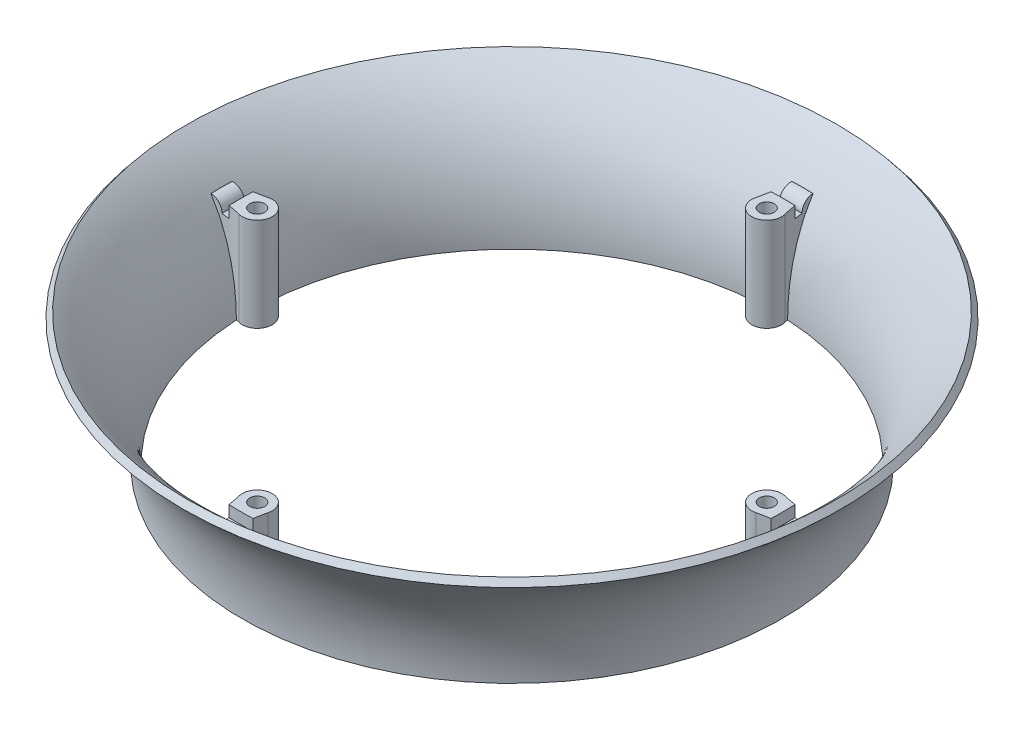
SolidWorks part; units mm, degrees
ref_plane "Front Plane" through (0, 0, 0) normal (0, 0, 1) x (1, 0, 0)
ref_plane "Top Plane" through (0, 0, 0) normal (0, 1, 0) x (1, 0, 0)
ref_plane "Right Plane" through (0, 0, 0) normal (1, 0, 0) x (0, 0, -1)
sketch "Sketch1" plane through (0, 0, 0) normal (0, 0, 1) x (1, 0, 0)
  line L0 (-25.5, 30) -> (-25.5, 0) construction
  line L1 (-25.5, 0) -> (-70, 0) construction
  line L2 (0, 0) -> (0, 35) construction
  line L3 (-70, 0) -> (-86.7157, 35) construction
  arc A0 (-70, 0) -> (-86.7157, 35) centre (-115, 0) ccw
  dimension "D1" = 35
  dimension "D5" = 45
  dimension "D2" = 30
  dimension "D3" = 70
  dimension "D4" = 25.5
  dimension "D7" = 35
revolve "Revolve-Thin1" add sketch "Sketch1" angle 360 about L2 wall 2
ref_plane "Plane1" through (0, 25, 0) normal (0, -1, 0) x (-1, 0, 0)
sketch "Sketch2" plane through (0, 25, 0) normal (0, -1, 0) x (-1, 0, 0)
  line L0 (-68, 0) -> (-86.7157, 0) construction
  line L1 (-86.7157, -4) -> (-86.7157, 4)
  line L2 (-4, 86.7157) -> (4, 86.7157)
  line L3 (0, 68) -> (0, 86.7157) construction
  line L4 (86.7157, 4) -> (86.7157, -4)
  line L5 (68, 0) -> (86.7157, 0) construction
  line L6 (4, -86.7157) -> (-4, -86.7157)
  line L7 (0, -68) -> (0, -86.7157) construction
  circle A0 centre (-68, 0) radius 2
  arc A1 (-68.9608, -3.8829) -> (-68.9608, 3.8829) centre (-68, 0) ccw
  circle A2 centre (0, 0) radius 86.7157 construction
  arc A3 (-86.6245, 3.9763) -> (-86.6245, -3.9763) centre (0, 0) ccw
  arc A4 (-68.9608, 3.8829) -> (-86.7157, 4) centre (-77.6082, 38.8289) cw
  arc A5 (-68.9608, -3.8829) -> (-86.7157, -4) centre (-77.6082, -38.8289) ccw
  arc A6 (3.8829, 68.9608) -> (4, 86.7157) centre (38.8289, 77.6082) cw
  arc A7 (-3.8829, 68.9608) -> (3.8829, 68.9608) centre (0, 68) ccw
  circle A8 centre (0, 68) radius 2
  arc A9 (-3.8829, 68.9608) -> (-4, 86.7157) centre (-38.8289, 77.6082) ccw
  arc A10 (68.9608, -3.8829) -> (86.7157, -4) centre (77.6082, -38.8289) cw
  arc A11 (68.9608, 3.8829) -> (68.9608, -3.8829) centre (68, 0) ccw
  circle A12 centre (68, 0) radius 2
  arc A13 (68.9608, 3.8829) -> (86.7157, 4) centre (77.6082, 38.8289) ccw
  arc A14 (-3.8829, -68.9608) -> (-4, -86.7157) centre (-38.8289, -77.6082) cw
  arc A15 (3.8829, -68.9608) -> (-3.8829, -68.9608) centre (0, -68) ccw
  circle A16 centre (0, -68) radius 2
  arc A17 (3.8829, -68.9608) -> (4, -86.7157) centre (38.8289, -77.6082) ccw
  point P10 (-86.7157, 0)
  dimension "D1" = 4
  dimension "D2" = 8
  dimension "D4" = 36
  dimension "D5" = 68
  dimension "D3" = 8
  dimension "D6" = 4
extrude "Boss-Extrude1" add sketch "Sketch2" along normal up to surface (25 mm away) contours A17 A15 A14 L6 A16 | A13 A11 A10 L4 A12 | A9 A7 A6 L2 A8 | A5 A1 A4 A3 A0 region at (76.0881, 25, 0) region at (0, 25, -76.1075) region at (-76.1075, 25, 0) region at (0, 25, 76.1075) up to face at (0, 0, -72)
sketch "Sketch3" plane through (0, 0, 0) normal (0, 0, 1) x (1, 0, 0)
  line L0 (-72, 0) -> (-99.1272, 0)
  line L1 (-99.1272, 0) -> (-99.1272, 33.4444)
  line L3 (-99.1272, 33.4444) -> (-87.9728, 33.4444)
  arc A0 (-70, 0) -> (-86.7157, 35) centre (-115, 0) ccw construction
  arc A4 (-72, 0) -> (-87.9728, 33.4444) centre (-115, 0) ccw
  arc A5 (-72, 0) -> (-87.9728, 33.4444) centre (-115, 0) ccw
  dimension "D1" = 2
revolve "Cut-Revolve1" cut sketch "Sketch3" angle 360 about L2
sketch "Sketch4" plane through (0, 25, 0) normal (0, 1, 0) x (1, 0, 0)
  circle A0 centre (0, 0) radius 74.5
  circle A1 centre (0, 0) radius 72.4
  dimension "D1" = 149
  dimension "D2" = 2.1
extrude "Cut-Extrude1" cut sketch "Sketch4" against normal blind 3
fillet "Fillet1" radius 3 4 edges at (-74.5, 25, 0) (0, 25, 74.5) (74.5, 25, 0) (0, 25, -74.5)
